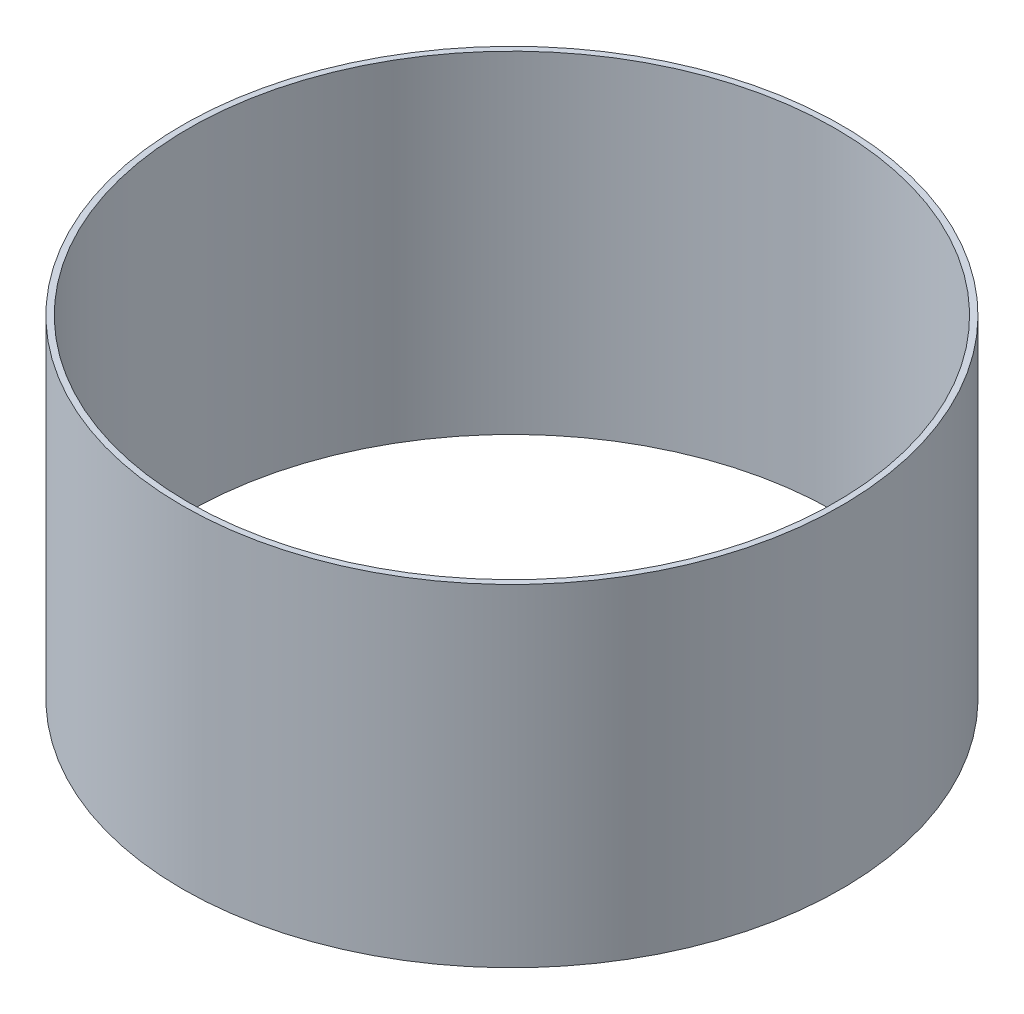
SolidWorks part; units mm, degrees
material "A-Glass Fiber"
ref_plane "Front Plane" through (0, 0, 0) normal (0, 0, 1) x (1, 0, 0)
ref_plane "Top Plane" through (0, 0, 0) normal (0, 1, 0) x (1, 0, 0)
ref_plane "Right Plane" through (0, 0, 0) normal (1, 0, 0) x (0, 0, -1)
sketch "Sketch1" plane through (0, 0, 0) normal (0, 1, 0) x (1, 0, 0)
  circle A0 centre (0, 0) radius 88.265
  circle A1 centre (0, 0) radius 86.6775
  dimension "D1" = 1.5875
  dimension "D2" = 176.53
extrude "Boss-Extrude1" add sketch "Sketch1" along normal blind 88.9
